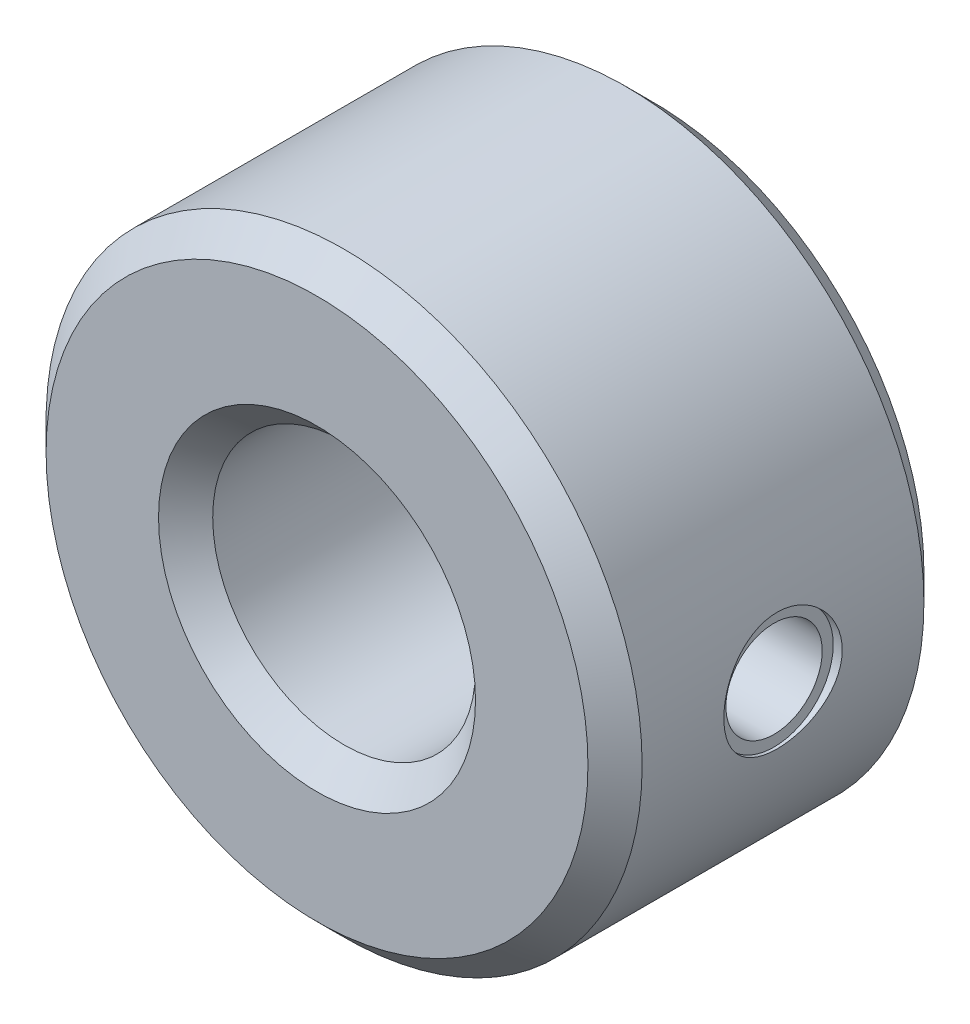
SolidWorks part; units mm, degrees
material "AISI 1020"
ref_plane "Front" through (0, 0, 0) normal (0, 0, 1) x (1, 0, 0)
ref_plane "Top" through (0, 0, 0) normal (0, 1, 0) x (1, 0, 0)
ref_plane "Right" through (0, 0, 0) normal (1, 0, 0) x (0, 0, -1)
ref_axis "side-side" through (80.9, 0, 0) along (-1, 0, 0)
ref_axis "up-down" through (0, 50, 0) along (0, -1, 0)
ref_axis "front-back" through (0, 0, -80.9) along (0, 0, 1)
sketch "Sketch1" plane through (0, 0, 0) normal (1, 0, 0) x (0, 0, -1)
  line L3 (-3.1, 5) -> (-3.1, 2.925)
  line L7 (-2.6, 2.425) -> (-3.1, 2.925)
  line L11 (2.6, 2.425) -> (-2.6, 2.425)
  line L14 (-2.6, 5.5) -> (-3.1, 5)
  line L19 (2.6, 5.5) -> (-2.6, 5.5)
  line L23 (3.1, 5) -> (2.6, 5.5)
  line L27 (3.1, 5) -> (3.1, 2.925)
  line L30 (3.1, 2.925) -> (2.6, 2.425)
  line L32 (0, 0) -> (13.3017, 0) construction
revolve "Revolve1" add sketch "Sketch1" angle 360 about L32
sketch "Sketch4" plane through (0, 0, 0) normal (1, 0, 0) x (0, 0, -1)
  circle A0 centre (0, 0) radius 1.0922
  dimension "D1" = 2.1844
extrude "Cut-Extrude1" cut sketch "Sketch4" against normal blind 0.508 from offset 5.842
hole_wizard "#2-56 Tapped Hole2" positions "Sketch5" profile "Sketch6" tap size "#2-56" standard "ANSI Inch" end condition up to next
sketch "Sketch5" plane through (5.334, 0, 0) normal (1, 0, 0) x (0, 0, -1)
  point P0 (0, 0)
sketch "Sketch6" plane through (5.334, 0, 0) normal (0, 1, 0) x (0, 0, -1)
  line L0 (0, 0) -> (0, 2.909)
  line L1 (0, 2.909) -> (0.889, 2.909)
  line L2 (0.889, 2.909) -> (0.889, 0)
  line L5 (0.889, 0) -> (0, 0)
  line L11 (0, -6.35) -> (0, 107.95) construction
  dimension "Thread Major Dia." = 1.778
  dimension "Thru Tap Drill Depth" = 2.909
imported_body "Imported1" [suppressed]
